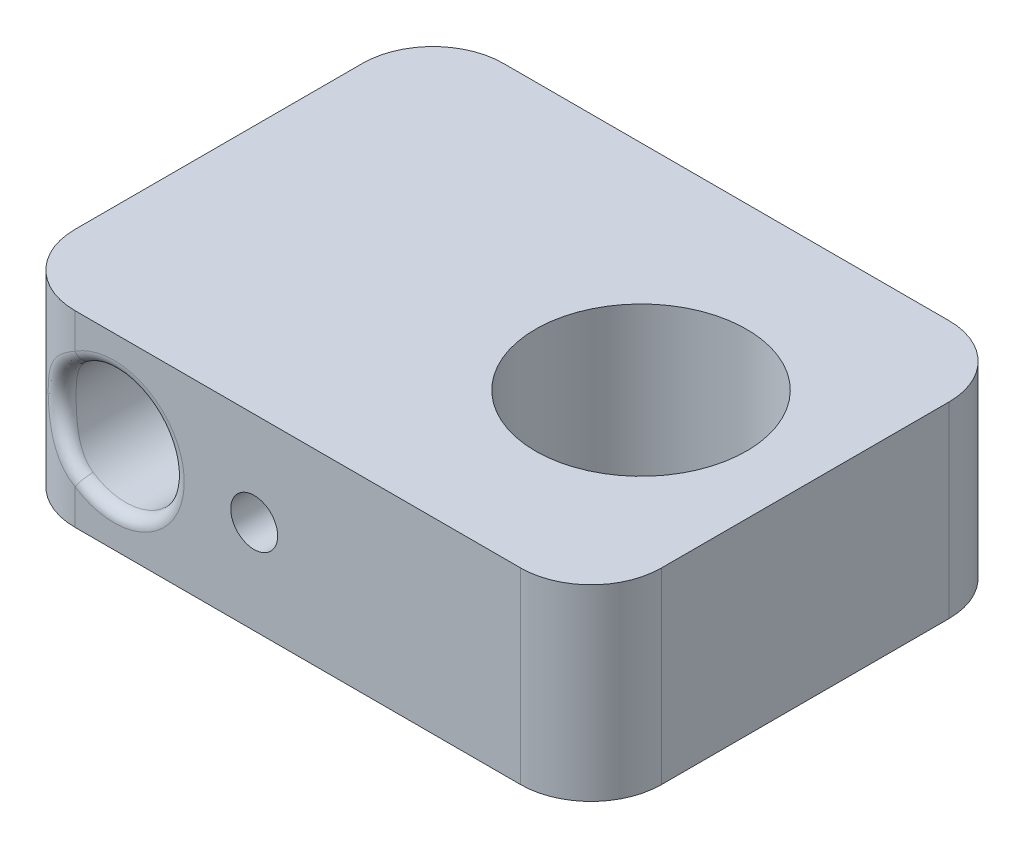
SolidWorks part; units mm, degrees
material "6061 Alloy"
ref_plane "Front Plane" through (0, 0, 0) normal (0, 0, 1) x (1, 0, 0)
ref_plane "Top Plane" through (0, 0, 0) normal (0, 1, 0) x (1, 0, 0)
ref_plane "Right Plane" through (0, 0, 0) normal (1, 0, 0) x (0, 0, -1)
sketch "Sketch1" plane through (0, 0, 0) normal (0, 1, 0) x (1, 0, 0)
  line L0 (-12.5, 9.13) -> (12.5, -9.13) construction
  line L1 (-12.5, 9.13) -> (12.5, 9.13)
  line L2 (-12.5, 9.13) -> (-12.5, -9.13)
  line L3 (-12.5, -9.13) -> (12.5, -9.13)
  line L4 (12.5, 9.13) -> (12.5, -9.13)
  dimension "D1" = 9.13
  dimension "D2" = 25
extrude "Boss-Extrude1" add sketch "Sketch1" along normal mid plane 8
hole_wizard "M10x1.0 Tapped Hole1" positions "Sketch3" profile "Sketch2" tap size "M10x1.0" standard "Ansi Metric"
sketch "Sketch3" plane through (0, 4, 0) normal (0, 1, 0) x (-1, 0, 0)
  line L1 (-12.5, 9.13) -> (-12.5, -9.13) construction
  point P0 (-5.5, 0)
  dimension "D1" = 7
sketch "Sketch2" plane through (5.5, 4, 0) normal (1, 0, 0) x (0, 0, 1)
  line L0 (0, 0) -> (0, 27.7039)
  line L1 (0, 27.7039) -> (4.5, 25)
  line L2 (4.5, 25) -> (4.5, 0)
  line L5 (4.5, 0) -> (0, 0)
  line L10 (0, 27.7039) -> (-4.5, 25) construction
  line L11 (0, -6.35) -> (0, 107.95) construction
  dimension "Tap Drill Dia." = 9
  dimension "Tap Drill Depth" = 25
  dimension "Drill Angle" = 118
cosmetic thread "Hole Thread1" parameters "D1"=8, "D2"=10
sketch "Sketch4" plane through (0, 0, 0) normal (0, 0, 1) x (1, 0, 0)
  line L0 (12.5, 4) -> (12.5, -4) construction
  circle A0 centre (-7.84, 0) radius 2.5
  circle A1 centre (-1.86, 0) radius 1
  dimension "D1" = 20.34
  dimension "D2" = 14.36
  dimension "D3" = 2
  dimension "D4" = 5
extrude "Cut-Extrude1" cut sketch "Sketch4" against normal through all and the other way through all
fillet "Fillet1" radius 3 4 edges at (-12.5, 0, -9.13) (-12.5, 0, 9.13) (12.5, 0, -9.13) (12.5, 0, 9.13)
fillet "Fillet2" radius 0.5 4 edges at (-10.2996, -0.4476, -9.0215) (-10.2996, 0.4476, 9.0215) (-5.34, 0, -9.13) (-5.34, 0, 9.13)
